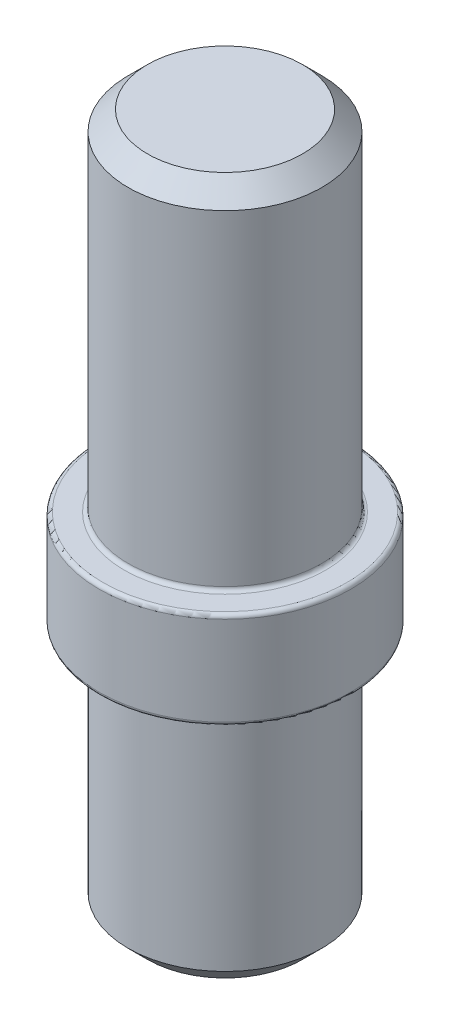
SolidWorks part; units mm, degrees
ref_plane "前视基准面" through (0, 0, 0) normal (0, 0, 1) x (1, 0, 0)
ref_plane "上视基准面" through (0, 0, 0) normal (0, 1, 0) x (1, 0, 0)
ref_plane "右视基准面" through (0, 0, 0) normal (1, 0, 0) x (0, 0, -1)
other "Configuration Table"
sketch "草图1" plane through (0, 0, 0) normal (0, 0, 1) x (1, 0, 0)
  line L0 (0, 23.0737) -> (0, -19.8109) construction
  line L1 (0, 23) -> (5, 23)
  line L2 (5, 23) -> (5, 5)
  line L3 (5, 5) -> (6.5, 5)
  line L4 (6.5, 5) -> (6.5, 0)
  line L5 (6.5, 0) -> (5, 0)
  line L6 (5, 0) -> (5, -13)
  line L7 (5, -13) -> (0, -13)
  line L8 (0, 23) -> (0, -13)
  dimension "D1" = 5
  dimension "D2" = 6.5
  dimension "D3" = 5
  dimension "D4" = 18
  dimension "D5" = 13
revolve "旋转1" add sketch "草图1" angle 360 about L0
chamfer "倒角1" distance 1 angle 45 2 edges at (0, -13, 5) (0, 23, 5)
fillet "圆角1" radius 0.2 4 edges at (0, 0, 5) (0, 0, 6.5) (0, 5, 6.5) (0, 5, 5)
